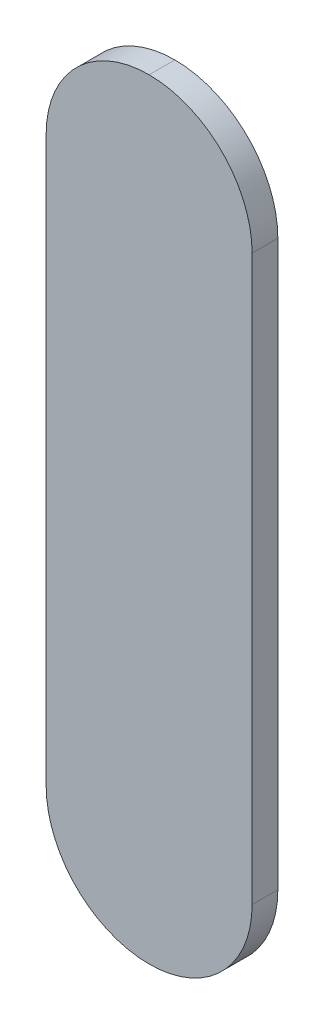
SolidWorks part; units mm, degrees
ref_plane "Front Plane" through (0, 0, 0) normal (0, 0, 1) x (1, 0, 0)
ref_plane "Top Plane" through (0, 0, 0) normal (0, 1, 0) x (1, 0, 0)
ref_plane "Right Plane" through (0, 0, 0) normal (1, 0, 0) x (0, 0, -1)
sketch "Sketch1" plane through (0, 0, 0) normal (0, 0, 1) x (1, 0, 0)
  line L1 (-39.5816, 40.1099) -> (40.4184, 40.1099)
  line L2 (-39.5816, 40.1099) -> (-39.5816, -259.0496)
  line L3 (-39.5816, -259.0496) -> (40.4184, -259.0496)
  line L4 (40.4184, 40.1099) -> (40.4184, -259.0496)
  dimension "D1" = 80
extrude "Boss-Extrude1" add sketch "Sketch1" along normal blind 10 contours L4 L3 L2 L1
fillet "Fillet1" radius 40 4 edges at (40.4184, -259.0496, 5) (-39.5816, -259.0496, 5) (40.4184, 40.1099, 5) (-39.5816, 40.1099, 5)
